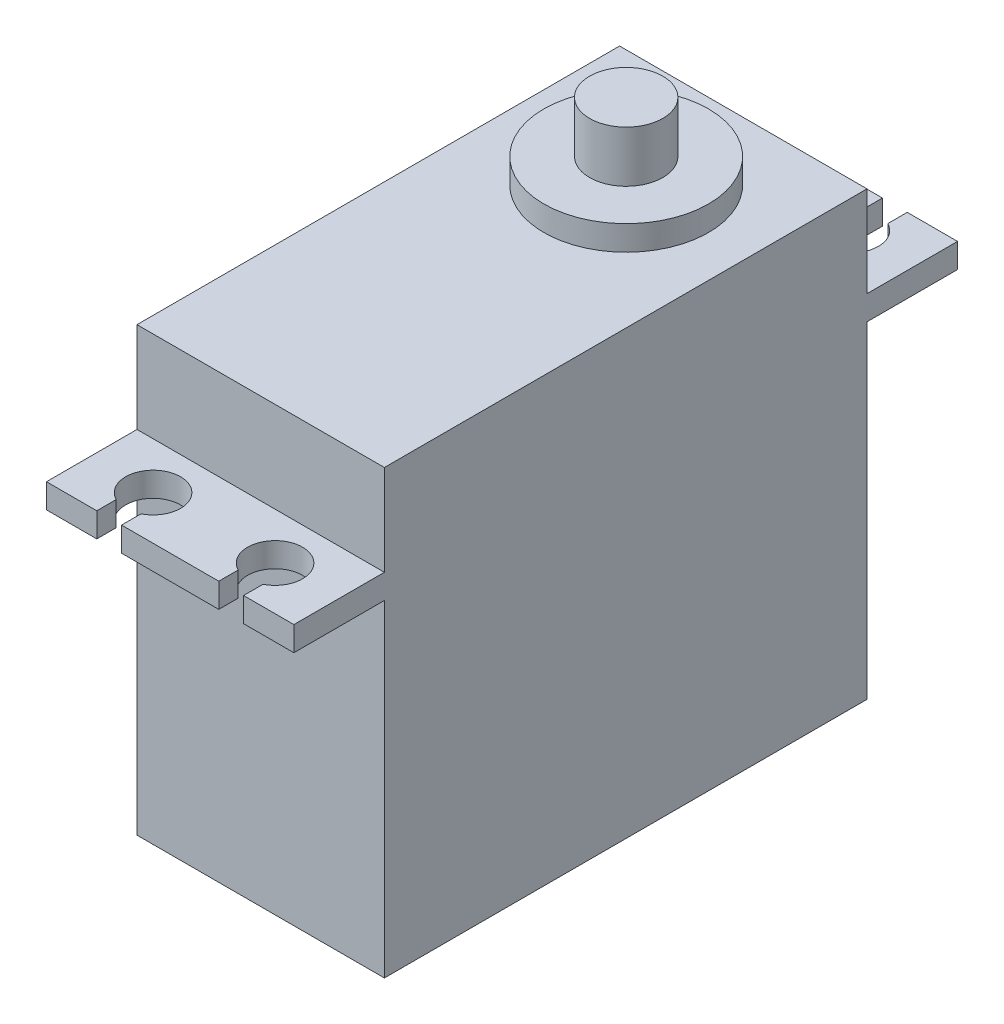
SolidWorks part; units mm, degrees
ref_plane "Front Plane" through (0, 0, 0) normal (0, 0, 1) x (1, 0, 0)
ref_plane "Top Plane" through (0, 0, 0) normal (0, 1, 0) x (1, 0, 0)
ref_plane "Right Plane" through (0, 0, 0) normal (1, 0, 0) x (0, 0, -1)
sketch "Sketch1" plane through (0, 0, 0) normal (0, 1, 0) x (1, 0, 0)
  line L1 (-10.14, -19.78) -> (10.14, -19.78)
  line L2 (-10.14, -19.78) -> (-10.14, 19.78)
  line L3 (-10.14, 19.78) -> (10.14, 19.78)
  line L4 (10.14, -19.78) -> (10.14, 19.78)
  line L5 (-10.14, -19.78) -> (10.14, 19.78) construction
  line L6 (-10.14, 19.78) -> (10.14, -19.78) construction
  point P0 (0, 0)
  dimension "D1" = 39.56
  dimension "D2" = 20.28
extrude "Boss-Extrude1" add sketch "Sketch1" along normal blind 36.24
sketch "Sketch2" plane through (0, 36.24, 0) normal (0, 1, 0) x (1, 0, 0)
  line L0 (0, 19.78) -> (0, -19.78) construction
  line L1 (10.14, 19.78) -> (-10.14, 19.78) construction
  line L2 (-10.14, -19.78) -> (10.14, -19.78) construction
  line L3 (-10.14, 16.93) -> (10.14, 16.93) construction
  line L4 (-10.14, 19.78) -> (-10.14, -19.78) construction
  line L5 (10.14, -19.78) -> (10.14, 19.78) construction
  circle A0 centre (0, 10.18) radius 6.75
  dimension "D1" = 13.5
  dimension "D2" = 2.85
extrude "Boss-Extrude2" add sketch "Sketch2" along normal blind 2.03
sketch "Sketch3" plane through (0, 0, -19.78) normal (0, 0, -1) x (-1, 0, 0)
  line L0 (-10.14, 36.24) -> (-10.14, 0) construction
  line L1 (-10.14, 28.8) -> (10.14, 28.8)
  line L2 (-10.14, 28.8) -> (-10.14, 26.8)
  line L3 (-10.14, 26.8) -> (10.14, 26.8)
  line L4 (10.14, 28.8) -> (10.14, 26.8)
  line L5 (10.14, 36.24) -> (10.14, 0) construction
  line L7 (-10.14, 0) -> (10.14, 0) construction
  dimension "D1" = 26.8
  dimension "D2" = 2
extrude "Boss-Extrude3" add sketch "Sketch3" along normal blind 7.42
sketch "Sketch4" plane through (0, 0, 19.78) normal (0, 0, 1) x (1, 0, 0)
  line L0 (-10.14, 36.24) -> (-10.14, 0) construction
  line L1 (-10.14, 28.8) -> (10.14, 28.8)
  line L2 (-10.14, 28.8) -> (-10.14, 26.8)
  line L3 (-10.14, 26.8) -> (10.14, 26.8)
  line L4 (10.14, 28.8) -> (10.14, 26.8)
  line L5 (10.14, 36.24) -> (10.14, 0) construction
  line L6 (-10.14, 0) -> (10.14, 0) construction
  dimension "D1" = 26.8
  dimension "D2" = 2
extrude "Boss-Extrude4" add sketch "Sketch4" along normal blind 7.42
sketch "Sketch5" plane through (0, 36.24, 0) normal (0, 1, 0) x (1, 0, 0)
  line L0 (-6.016, 25.6075) -> (-6.016, 27.2)
  line L1 (-5, -23.6) -> (5, -23.6) construction
  line L2 (-5, -23.6) -> (-5, 23.6) construction
  line L3 (-5, 23.6) -> (5, 23.6) construction
  line L4 (5, -23.6) -> (5, 23.6) construction
  line L5 (-5, -23.6) -> (5, 23.6) construction
  line L6 (-5, 23.6) -> (5, -23.6) construction
  line L7 (-10.14, 27.2) -> (10.14, 27.2) construction
  line L8 (-10.14, 27.2) -> (-10.14, -27.2) construction
  line L9 (-10.14, -27.2) -> (10.14, -27.2) construction
  line L10 (10.14, 27.2) -> (10.14, -27.2) construction
  line L11 (-3.984, 25.6075) -> (-3.984, 27.2)
  line L12 (3.984, 25.6075) -> (3.984, 27.2)
  line L13 (6.016, 25.6075) -> (6.016, 27.2)
  line L14 (-6.016, -25.6075) -> (-6.016, -27.2)
  line L15 (-3.984, -25.6075) -> (-3.984, -27.2)
  line L16 (3.984, -25.6075) -> (3.984, -27.2)
  line L17 (6.016, -25.6075) -> (6.016, -27.2)
  line L18 (-6.016, -27.2) -> (-3.984, -27.2)
  line L19 (3.984, -27.2) -> (6.016, -27.2)
  line L20 (-6.016, 27.2) -> (-3.984, 27.2)
  line L21 (3.984, 27.2) -> (6.016, 27.2)
  arc A0 (-6.016, 25.6075) -> (-3.984, 25.6075) centre (-5, 23.6) ccw
  arc A1 (3.984, 25.6075) -> (6.016, 25.6075) centre (5, 23.6) ccw
  arc A2 (-3.984, -25.6075) -> (-6.016, -25.6075) centre (-5, -23.6) ccw
  arc A3 (6.016, -25.6075) -> (3.984, -25.6075) centre (5, -23.6) ccw
  point P0 (0, 0)
  dimension "D3" = 4.5
  dimension "D1" = 47.2
  dimension "D2" = 10
  dimension "D4" = 2.032
extrude "Cut-Extrude1" cut sketch "Sketch5" against normal through all
sketch "Sketch6" plane through (0, 38.27, 0) normal (0, 1, 0) x (1, 0, 0)
  circle A0 centre (0, 10.18) radius 3
  dimension "D1" = 6
extrude "Boss-Extrude5" add sketch "Sketch6" along normal blind 4.2
